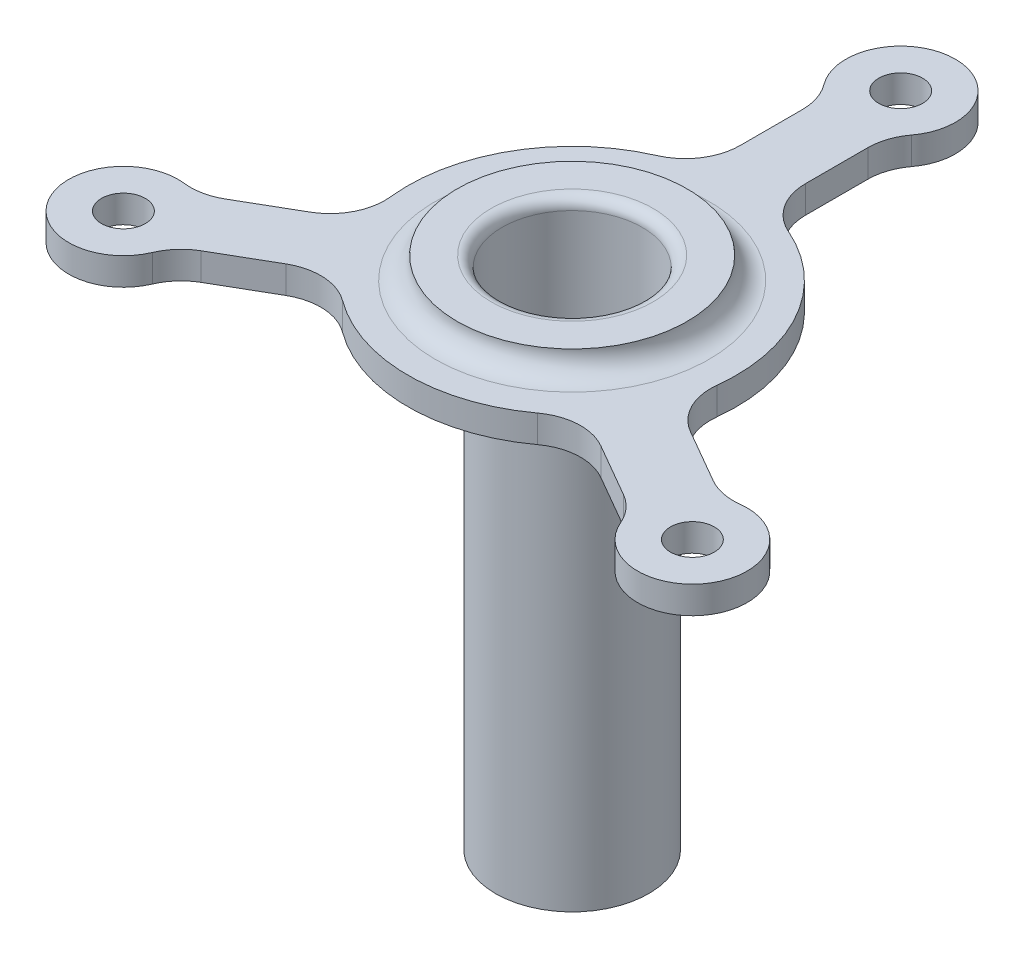
SolidWorks part; units mm, degrees
ref_plane "前视基准面" through (0, 0, 0) normal (0, 0, 1) x (1, 0, 0)
ref_plane "上视基准面" through (0, 0, 0) normal (0, 1, 0) x (1, 0, 0)
ref_plane "右视基准面" through (0, 0, 0) normal (1, 0, 0) x (0, 0, -1)
sketch "草图1" plane through (0, 0, 0) normal (0, 1, 0) x (1, 0, 0)
  line L0 (0, 30) -> (0, 0) construction
  line L1 (-3, 26) -> (-3, 14.6969)
  line L2 (3, 26) -> (3, 14.6969)
  line L3 (24.0167, -10.4019) -> (14.2279, -4.7504)
  line L4 (21.0167, -15.5981) -> (11.2279, -9.9465)
  line L5 (-21.0167, -15.5981) -> (-11.2279, -9.9465)
  line L6 (-24.0167, -10.4019) -> (-14.2279, -4.7504)
  circle A0 centre (0, 30) radius 2
  circle A1 centre (25.9808, -15) radius 2
  circle A2 centre (-25.9808, -15) radius 2
  circle A3 centre (0, 30) radius 5
  circle A4 centre (25.9808, -15) radius 5
  circle A5 centre (-25.9808, -15) radius 5
  circle A6 centre (0, 0) radius 6.4
  circle A7 centre (0, 0) radius 15
  point P9 (0, 0)
  point P15 (0, 0)
  point P30 (0, 0)
  dimension "D2" = 4
  dimension "D3" = 3
  dimension "D4" = 10
  dimension "D5" = 3
  dimension "D6" = 12.8
  dimension "D7" = 30
  dimension "D1" = 30
  dimension "D8" = 6
  dimension "D9" = 3
extrude "凸台-拉伸1" add sketch "草图1" against normal blind 2.5 contours A5 A2 | A7 L6 A5 L5 | A7 A6 | A7 L4 A4 L3 | A4 A1 | L0 A3 L1 A7 | A3 L0 A7 L2 | A0 A3 region at (-1.5364, 0, -25.3907) region at (1.5307, 0, -20.1128) region at (-1.5307, 0, -20.1128) region at (1.465, 0, -14.5019) region at (-17.4182, 0, 10.0564) region at (17.4182, 0, 10.0564) region at (-21.9262, 0, 12.323) region at (28.6578, 0, 10.9455)
sketch "草图2" plane through (0, 0, 0) normal (0, 1, 0) x (1, 0, 0)
  circle A0 centre (0, 0) radius 10.5
  circle A1 centre (0, 0) radius 6.4 construction
  circle A2 centre (0, 0) radius 6.4
extrude "凸台-拉伸2" add sketch "草图2" along normal blind 2
sketch "草图3" plane through (0, -2.5, 0) normal (0, -1, 0) x (1, 0, 0)
  circle A0 centre (0, 0) radius 11
  dimension "D1" = 22
extrude "切除-拉伸1" cut sketch "草图3" against normal blind 1
sketch "草图4" plane through (0, -1.5, 0) normal (0, -1, 0) x (1, 0, 0)
  circle A0 centre (0, 0) radius 6.4 construction
  circle A1 centre (0, 0) radius 6.4
  circle A2 centre (0, 0) radius 7
  dimension "D1" = 14
extrude "凸台-拉伸3" add sketch "草图4" along normal blind 42
fillet "圆角2" radius 1 2 edges at (0, -1.5, -7) (0, 2, 6.4)
sketch "草图5" plane through (0, -43.5, 0) normal (0, -1, 0) x (1, 0, 0)
  circle A0 centre (0, 0) radius 4
  circle A1 centre (0, 0) radius 7
  circle A2 centre (0, 0) radius 7
  dimension "D2" = 8
  dimension "D1" = 0
extrude "凸台-拉伸4" add sketch "草图5" along normal blind 1.5
fillet "圆角3" radius 5 12 edges at (21.0167, -1.25, 15.5981) (11.2279, -1.25, 9.9465) (24.0167, -1.25, 10.4019) (14.2279, -1.25, 4.7504) (-24.0167, -1.25, 10.4019) (-21.0167, -1.25, 15.5981) (-11.2279, -1.25, 9.9465) (-14.2279, -1.25, 4.7504) (-3, -1.25, -26) (3, -1.25, -26) (-3, -1.25, -14.6969) (3, -1.25, -14.6969)
fillet "圆角4" radius 2 1 edges at (0, 0, 10.5)
